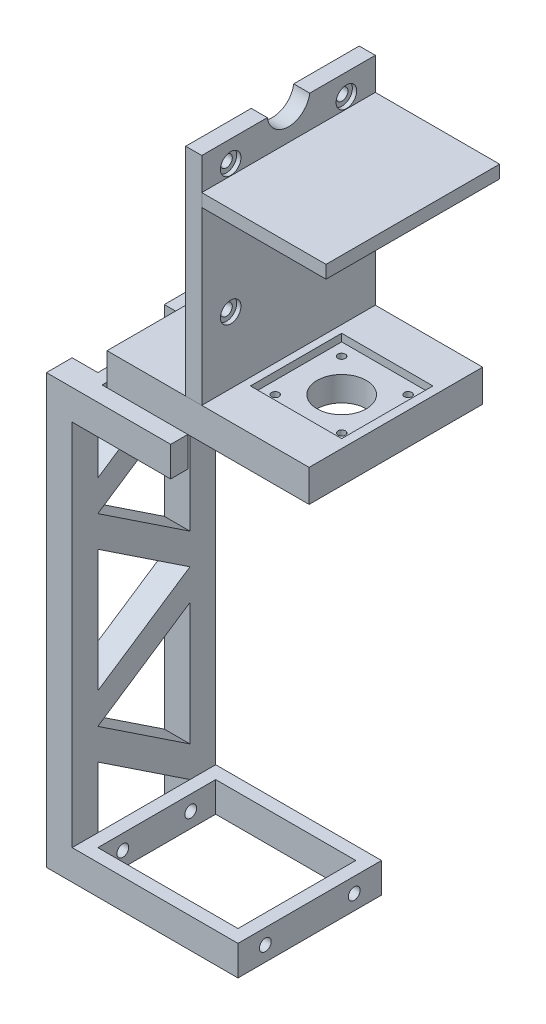
SolidWorks part; units mm, degrees
note: The reader was unsure of these and kept them because the rebuilt part matched: shared geometry of "Sketch11<5>", "Sketch13<3>".
ref_plane "Front Plane" through (0, 0, 0) normal (0, 0, 1) x (1, 0, 0)
ref_plane "Top Plane" through (0, 0, 0) normal (0, 1, 0) x (1, 0, 0)
ref_plane "Right Plane" through (0, 0, 0) normal (1, 0, 0) x (0, 0, -1)
sketch "Sketch1" plane through (0, 0, 0) normal (0, 1, 0) x (1, 0, 0)
  line L1 (-32.7, -27.5) -> (32.7, -27.5)
  line L2 (-32.7, -27.5) -> (-32.7, 27.5)
  line L3 (-32.7, 27.5) -> (32.7, 27.5)
  line L4 (32.7, -27.5) -> (32.7, 27.5)
  line L5 (-32.7, -27.5) -> (32.7, 27.5) construction
  line L6 (-32.7, 27.5) -> (32.7, -27.5) construction
  line L7 (-38.7, -33.5) -> (38.7, -33.5)
  line L8 (-38.7, -33.5) -> (-38.7, 33.5)
  line L9 (-38.7, 33.5) -> (38.7, 33.5)
  line L10 (38.7, -33.5) -> (38.7, 33.5)
  line L11 (-38.7, -33.5) -> (38.7, 33.5) construction
  line L12 (-38.7, 33.5) -> (38.7, -33.5) construction
  circle A0 centre (-12.4, 0) radius 4
  circle A1 centre (53.6, 0) radius 4
  point P0 (0, 0)
  point P6 (0, 0)
  dimension "D3" = 8
  dimension "D1" = 20.3
  dimension "D2" = 14.9
  dimension "D4" = 66
  dimension "D5" = 6
  dimension "D6" = 6
  dimension "D7" = 55
extrude "Boss-Extrude1" add sketch "Sketch1" along normal blind 14 contours L7 L10 L9 L8 L4 L1 L2 L3
sketch "Sketch4" plane through (0, 0, 0) normal (0, 1, 0) x (1, 0, 0)
  line L0 (-38.7, -33.5) -> (-50.7, -33.5)
  line L1 (-50.7, -33.5) -> (-50.7, -21.5)
  line L2 (-50.7, -21.5) -> (-38.7, -21.5)
  line L3 (-38.7, -33.5) -> (-38.7, 33.5) construction
  line L4 (-38.7, -21.5) -> (-38.7, -33.5)
  line L5 (-38.7, 33.5) -> (-50.7, 33.5)
  line L6 (-50.7, 33.5) -> (-50.7, 21.5)
  line L7 (-50.7, 21.5) -> (-38.7, 21.5)
  line L8 (-38.7, 21.5) -> (-38.7, 33.5)
  point P10 (-50.2185, 21.1217)
  dimension "D1" = 12
  dimension "D2" = 12
extrude "Boss-Extrude2" add sketch "Sketch4" along normal blind 200
sketch "Sketch5" plane through (0, 200, 0) normal (0, 1, 0) x (1, 0, 0)
  line L0 (-38.7, -33.5) -> (38.7, -33.5) construction
  line L1 (-38.7, 33.5) -> (-32.7, 33.5)
  line L2 (-38.7, 33.5) -> (-38.7, -33.5)
  line L3 (-38.7, -33.5) -> (-32.7, -33.5)
  line L4 (-32.7, 33.5) -> (-32.7, -33.5)
  line L7 (-32.7, -27.5) -> (-32.7, 27.5) construction
extrude "Boss-Extrude3" add sketch "Sketch5" against normal blind 14
sketch "Sketch6" plane through (-50.7, 0, 0) normal (-1, 0, 0) x (0, 0, 1)
  line L0 (-21.5, 186) -> (21.5, 157.4103)
  line L1 (21.5, 200) -> (21.5, 0) construction
  line L2 (-21.5, 171.5897) -> (21.5, 143)
  line L3 (21.5, 143) -> (-21.5, 114.4103)
  line L4 (-21.5, 200) -> (-21.5, 0) construction
  line L5 (21.5, 128.5897) -> (-21.5, 100)
  line L6 (21.5, 157.4103) -> (21.5, 143)
  line L7 (21.5, 128.5897) -> (21.5, 143)
  line L8 (-21.5, 114.4103) -> (-21.5, 100)
  line L9 (-21.5, 186) -> (-21.5, 171.5897)
  line L10 (-21.5, 100) -> (21.5, 71.4103)
  line L11 (21.5, 71.4103) -> (21.5, 57)
  line L12 (21.5, 57) -> (-21.5, 85.5897)
  line L13 (-21.5, 85.5897) -> (-21.5, 100)
  line L14 (21.5, 57) -> (-21.5, 28.4103)
  line L15 (-21.5, 28.4103) -> (-21.5, 14)
  line L16 (-21.5, 14) -> (21.5, 42.5897)
  line L17 (21.5, 42.5897) -> (21.5, 57)
  line L18 (-21.5, 200) -> (-21.5, 186) construction
  line L19 (-21.5, 14) -> (-21.5, 0) construction
  point P17 (-21.5, 17.5477)
  point P20 (-21.5, 0.2932)
  point P21 (0, 0)
  point P22 (-21.5, 195.0396)
  point P25 (-21.5, 186)
  point P26 (0, 0)
  point P27 (-21.5, 179.0446)
  point P28 (-21.5, 186)
  point P30 (-21.5, 175.679)
  point P31 (-21.5, 14)
  point P34 (-21.5, 25.5929)
  point P35 (-21.5, 14)
  point P36 (-21.5, 26.0997)
  point P37 (-21.5, 186)
  point P39 (-21.5, 27.7285)
  line M18 (-21.5, 0) -> (-21.5, 200)
  dimension "D1" = 12
extrude "Boss-Extrude4" add sketch "Sketch6" against normal up to surface (12 mm away) contours L6 L0 L2 M18 | L5 L7 L3 M18 | L12 L11 L10 M18 | L16 L17 L14 M18 up to face at (-38.7, 100, 27.5)
sketch "Sketch2" plane through (38.7, 0, 0) normal (1, 0, 0) x (0, 0, -1)
  line L0 (-20.75, 7) -> (20.75, 7) construction
  line L1 (33.5, 14) -> (33.5, 0) construction
  circle A0 centre (-20.75, 7) radius 2.75
  circle A1 centre (20.75, 7) radius 2.75
  point P4 (33.5, 7)
  point P5 (0, 7)
  dimension "D1" = 5.5
  dimension "D2" = 41.5
extrude "Cut-Extrude1" cut sketch "Sketch2" against normal up to surface (6 mm away) up to face at (32.7, 7, 0)
sketch "Sketch3" plane through (-32.7, 0, 0) normal (1, 0, 0) x (0, 0, -1)
  line L0 (15.85, 7) -> (-15.85, 7) construction
  line L3 (-15.85, 7) -> (-33.5, 7) construction
  line L4 (-33.5, 14) -> (-33.5, 0) construction
  circle A0 centre (15.85, 7) radius 2.75
  circle A1 centre (-15.85, 7) radius 2.75
  point P0 (0, 7)
  dimension "D2" = 5.5
  dimension "D1" = 31.7
extrude "Cut-Extrude2" cut sketch "Sketch3" against normal up to surface (6 mm away) up to face at (-38.7, 7, 0)
sketch "Sketch7" plane through (-32.7, 0, -32.7) normal (1, 0, 0) x (0, 0, -1)
  line L0 (-16.85, 193) -> (-48.55, 193) construction
  line L1 (-66.2, 200) -> (0.8, 200) construction
  line L2 (-66.2, 186) -> (-66.2, 200) construction
  line L3 (-48.55, 193) -> (-66.2, 193) construction
  circle A0 centre (-16.85, 193) radius 2.75
  circle A1 centre (-48.55, 193) radius 2.75
  point P0 (-32.7, 193)
  point P1 (19.882, 65.69)
  point P7 (-32.7, 200)
  point P13 (-66.2, 193)
  point P14 (-66.2, 193)
  dimension "D2" = 5.5
  dimension "D1" = 31.7
extrude "Cut-Extrude3" cut sketch "Sketch7" against normal through all
ref_plane "Plane1" through (0, 215, 0) normal (0, 1, 0) x (1, 0, 0)
sketch "Sketch8" plane through (-32.7, 0, 0) normal (1, 0, 0) x (0, 0, -1)
  line L0 (-33.5, 186) -> (33.5, 186) construction
  line L1 (-33.5, 200) -> (-25.5, 200)
  line L2 (-33.5, 200) -> (-33.5, 186)
  line L3 (-33.5, 186) -> (-25.5, 186)
  line L4 (-25.5, 200) -> (-25.5, 186)
  line L6 (33.5, 200) -> (25.5, 200)
  line L7 (33.5, 200) -> (33.5, 186)
  line L8 (33.5, 186) -> (25.5, 186)
  line L9 (25.5, 200) -> (25.5, 186)
  dimension "D1" = 8
extrude "Boss-Extrude5" add sketch "Sketch8" along normal blind 40
sketch "Sketch9" plane through (0, 215, 0) normal (0, 1, 0) x (1, 0, 0)
  line L0 (-38.7, 21.5) -> (-38.7, -21.5) construction
  line L1 (-5.713, 40.5) -> (78.9, 40.5)
  line L2 (-5.713, 40.5) -> (-5.713, -40.5)
  line L3 (-5.713, -40.5) -> (78.9, -40.5)
  line L4 (78.9, 40.5) -> (78.9, -40.5)
  line L5 (-32.7, -25.5) -> (-32.7, 25.5) construction
  line L7 (7.3, 40.5) -> (-15.4135, 40.5)
  line L8 (7.3, 40.5) -> (7.3, -40.5)
  line L9 (7.3, -40.5) -> (-15.4135, -40.5)
  line L10 (-15.4135, 40.5) -> (-15.4135, -40.5)
  line L11 (7.3, 33.5) -> (7.3, 25.5) construction
  point P4 (-15.8358, -37.5292)
  point P5 (78.9, 0)
  point P6 (6.7107, 36.3731)
  point P9 (-38.7, 0)
  point P10 (-5.713, 0)
  point P13 (53.6, 0)
  point P20 (0, 0)
  point P21 (0, 0)
  point P22 (0, 0)
  point P23 (6.8777, 37.1246)
  point P26 (-15.4135, 0)
  point P27 (-5.713, 29.3)
  dimension "D1" = 81
  dimension "D2" = 25.3
  dimension "D3" = 86.3
  dimension "D4" = 81
extrude "Boss-Extrude6" add sketch "Sketch9" along normal blind 15 separate body contours L7 L10 L9 L8 L3 L2 L1 | L8 L1 L2 L3 | L1 L8 L3 L4
sketch "Sketch10" plane through (0, 230, 0) normal (0, 1, 0) x (1, 0, 0)
  line L1 (32.3, -21.3) -> (74.9, -21.3)
  line L2 (32.3, -21.3) -> (32.3, 21.3)
  line L3 (32.3, 21.3) -> (74.9, 21.3)
  line L4 (74.9, -21.3) -> (74.9, 21.3)
  line L5 (32.3, -21.3) -> (74.9, 21.3) construction
  line L6 (32.3, 21.3) -> (74.9, -21.3) construction
  line L8 (78.9, 40.5) -> (78.9, -40.5) construction
  point P0 (53.6, 0)
  point P5 (0, 0)
  point P6 (0, 0)
  point P7 (0, 0)
  point P11 (0, 0)
  point P12 (0, 0)
  point P13 (78.9, 0)
  dimension "D1" = 42.6
  dimension "D2" = 42.6
  dimension "D3" = 4
extrude "Cut-Extrude4" cut sketch "Sketch10" against normal blind 3.5
sketch "Sketch11" plane through (0, 226.5, -221.5) normal (0, -1, 0) x (1, 0, 0)
  line L0 (74.9, 200.2) -> (32.3, 200.2) construction
  line L1 (38.1, 206) -> (69.1, 206) construction
  line L2 (38.1, 206) -> (38.1, 237) construction
  line L3 (38.1, 237) -> (69.1, 237) construction
  line L4 (69.1, 206) -> (69.1, 237) construction
  line L5 (38.1, 206) -> (69.1, 237) construction
  line L6 (38.1, 237) -> (69.1, 206) construction
  line L7 (74.9, 242.8) -> (74.9, 200.2) construction
  circle A0 centre (38.1, 237) radius 1.75
  circle A1 centre (69.1, 237) radius 1.75
  circle A2 centre (69.1, 206) radius 1.75
  circle A3 centre (38.1, 206) radius 1.75
  circle A4 centre (38.1, 237) radius 3
  circle A5 centre (69.1, 237) radius 3
  circle A6 centre (69.1, 206) radius 3
  circle A7 centre (38.1, 206) radius 3
  circle A8 centre (53.6, 221.5) radius 11.5
  point P0 (53.6, 221.5)
  point P5 (0, 0)
  point P14 (0, 0)
  point P17 (53.6, 200.2)
  point P18 (0, 0)
  point P21 (74.9, 221.5)
  dimension "D1" = 3.5
  dimension "D4" = 6
  dimension "D5" = 23
  dimension "D2" = 31
  dimension "D3" = 31
extrude "Cut-Extrude5" cut sketch "Sketch11" along normal up to surface (11.5 mm away) contours A1 | A0 | A3 | A2 | A8
extrude "Cut-Extrude6" cut sketch "Sketch11<5>" against normal blind 3 from surface
sketch "Sketch11<5>" plane through (0, 226.5, -221.5) normal (0, -1, 0) x (1, 0, 0) same geometry as "Sketch11"
ref_plane "Plane2" through (21.3, 0, 0) normal (-1, 0, 0) x (0, 0, 1)
sketch "Sketch13" plane through (21.3, 0, 0) normal (-1, 0, 0) x (0, 0, 1)
  line L0 (0, 332.3723) -> (0, 342.9574) construction
  line L1 (-27, 261) -> (27, 261) construction
  line L2 (-27, 261) -> (-27, 321) construction
  line L3 (-27, 321) -> (27, 321) construction
  line L4 (27, 261) -> (27, 321) construction
  line L5 (-27, 261) -> (27, 321) construction
  line L6 (-27, 321) -> (27, 261) construction
  line L7 (-40.5, 331) -> (40.5, 331)
  line L8 (-40.5, 331) -> (-40.5, 230)
  line L9 (-40.5, 230) -> (40.5, 230)
  line L10 (40.5, 331) -> (40.5, 230)
  line L11 (-10, 332.3723) -> (-10, 342.9574)
  line L12 (10, 332.3723) -> (10, 342.9574)
  line L14 (25.5, 200) -> (-25.5, 200) construction
  line L15 (-40.5, 230) -> (40.5, 230) construction
  circle A0 centre (-27, 321) radius 2.75
  circle A1 centre (27, 321) radius 2.75
  circle A2 centre (27, 261) radius 2.75
  circle A3 centre (-27, 261) radius 2.75
  arc A4 (-10, 332.3723) -> (10, 332.3723) centre (0, 332.3723) ccw
  arc A5 (10, 342.9574) -> (-10, 342.9574) centre (0, 342.9574) ccw
  circle A6 centre (27, 321) radius 4.8
  circle A7 centre (27, 261) radius 4.8
  circle A8 centre (-27, 261) radius 4.8
  circle A9 centre (-27, 321) radius 4.8
  point P0 (0, 291)
  point P14 (0, 331)
  point P15 (0, 337.6649)
  point P27 (0, 337.4703)
  point P28 (0, 328.7669)
  point P29 (0, 332.3723)
  point P32 (0, 200)
  dimension "D1" = 5.5
  dimension "D7" = 9.6
  dimension "D2" = 54
  dimension "D3" = 60
  dimension "D4" = 81
  dimension "D5" = 10
  dimension "D6" = 20
  dimension "D8" = 101
extrude "Boss-Extrude7" add sketch "Sketch13" against normal blind 5.5 separate body contours L10 L7 L8 L9 A3 L2 A0 L3 A1 L4 A2 L1 | A9 A0 | A6 A1 | A7 A2 | A8 A3
extrude "Boss-Extrude10" add sketch "Sketch13<3>" against normal blind 2 from surface at -5.5 contours A4 L11 L7 L8 L9 L10 L12 A9 A8 A7 A6
sketch "Sketch13<3>" plane through (21.3, 0, 0) normal (-1, 0, 0) x (0, 0, 1) same geometry as "Sketch13"
sketch "Sketch15" plane through (28.8, 0, 0) normal (1, 0, 0) x (0, 0, -1)
  line L1 (-40.5, 316) -> (40.5, 316)
  line L2 (-40.5, 316) -> (-40.5, 310)
  line L3 (-40.5, 310) -> (40.5, 310)
  line L4 (40.5, 316) -> (40.5, 310)
  line L7 (40.5, 230) -> (-40.5, 230) construction
  line L8 (-40.5, 331) -> (-40.5, 230) construction
  line L9 (40.5, 331) -> (40.5, 230) construction
  point P4 (-40.5, 316)
  point P6 (40.5, 310)
  point P10 (0, 0)
  point P12 (0, 0)
  dimension "D1" = 80
  dimension "D2" = 6
extrude "Boss-Extrude9" add sketch "Sketch15" along normal blind 58
